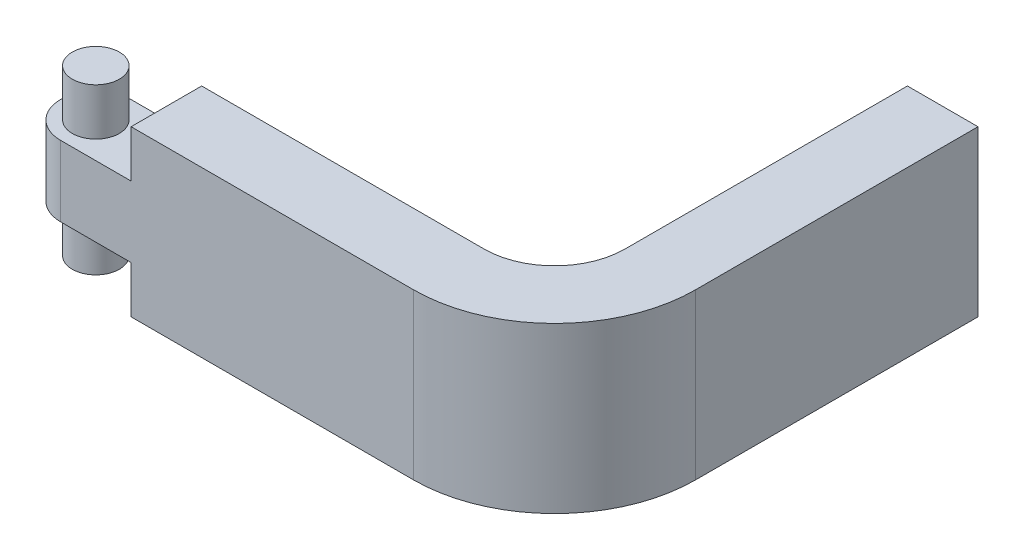
SolidWorks part; units mm, degrees
ref_plane "前视基准面" through (0, 0, 0) normal (0, 0, 1) x (1, 0, 0)
ref_plane "上视基准面" through (0, 0, 0) normal (0, 1, 0) x (1, 0, 0)
ref_plane "右视基准面" through (0, 0, 0) normal (1, 0, 0) x (0, 0, -1)
sketch "草图1" plane through (0, 0, 0) normal (0, 1, 0) x (1, 0, 0)
  line L0 (0, 0) -> (75, 0)
  line L1 (0, 15) -> (75, 15)
  line L4 (90, 30) -> (90, 90)
  line L5 (105, 30) -> (105, 90)
  line L6 (90, 90) -> (105, 90)
  arc A1 (0, 0) -> (0, 15) centre (0, 7.5) cw
  circle A3 centre (0, 7.5) radius 5
  arc A4 (75, 0) -> (105, 30) centre (75, 30) ccw
  arc A5 (75, 15) -> (90, 30) centre (75, 30) ccw
extrude "凸台-拉伸1" add sketch "草图1" along normal blind 7.5 and the other way blind 7.5
ref_plane "基准面4" through (0, 17.5, 0) normal (0, 1, 0) x (1, 0, 0)
sketch "草图2" plane through (0, 0, 0) normal (0, 1, 0) x (1, 0, 0)
  circle A0 centre (0, 7.5) radius 5
extrude "凸台-拉伸2" add sketch "草图2" against normal mid plane 35
ref_plane "基准面5" through (105, 7.5, -30) normal (0, 0, -1) x (-1, 0, 0)
sketch "草图3" plane through (0, 7.5, 0) normal (0, 1, 0) x (1, 0, 0)
  line L0 (90, 90) -> (90, 30)
  line L1 (75, 15) -> (15, 15)
  line L2 (75, 15) -> (0, 15) construction
  line L3 (15, 15) -> (15, 0)
  line L4 (0, 0) -> (75, 0) construction
  line L5 (15, 0) -> (75, 0)
  line L6 (105, 30) -> (105, 90)
  line L7 (105, 90) -> (90, 90)
  arc A0 (90, 30) -> (75, 15) centre (75, 30) cw
  arc A1 (75, 0) -> (105, 30) centre (75, 30) ccw
extrude "凸台-拉伸3" add sketch "草图3" along normal blind 10
mirror "镜向1" about plane through (0, 0, 0) normal (0, 1, 0) of "凸台-拉伸3"
